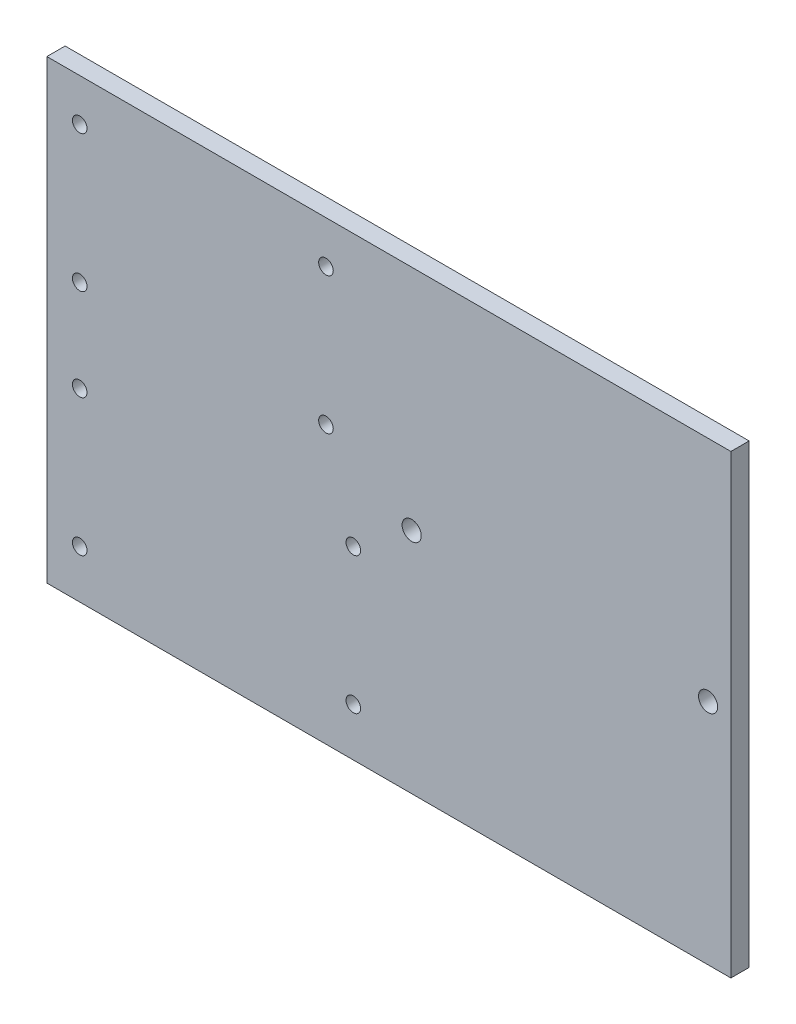
SolidWorks part; units mm, degrees
ref_plane "前视基准面" through (0, 0, 0) normal (0, 0, 1) x (1, 0, 0)
ref_plane "上视基准面" through (0, 0, 0) normal (0, 1, 0) x (1, 0, 0)
ref_plane "右视基准面" through (0, 0, 0) normal (1, 0, 0) x (0, 0, -1)
other "Configuration Table"
sketch "草图1" plane through (0, 0, 0) normal (0, 0, 1) x (1, 0, 0)
  line L0 (97.0297, -3.5891) -> (-52.9703, -3.5891) construction
  line L1 (-52.9703, 46.4109) -> (97.0297, 46.4109)
  line L2 (-52.9703, 46.4109) -> (-52.9703, -53.5891)
  line L3 (-52.9703, -53.5891) -> (97.0297, -53.5891)
  line L4 (97.0297, 46.4109) -> (97.0297, -53.5891)
  line L6 (27.0297, 29.2497) -> (92.0297, 29.2497) construction
  line L7 (27.0297, 29.2497) -> (27.0297, -33.8323) construction
  line L8 (27.0297, -33.8323) -> (92.0297, -33.8323) construction
  line L9 (92.0297, 29.2497) -> (92.0297, -33.8323) construction
  line L10 (-45.7673, -13.0209) -> (14.2327, -13.0209) construction
  line L11 (-45.7673, -13.0209) -> (-45.7673, -43.0209) construction
  line L12 (-45.7673, -43.0209) -> (14.2327, -43.0209) construction
  line L13 (14.2327, -13.0209) -> (14.2327, -43.0209) construction
  line L14 (-45.7673, 37.1291) -> (8.2327, 37.1291) construction
  line L15 (-45.7673, 37.1291) -> (-45.7673, 7.1291) construction
  line L16 (-45.7673, 7.1291) -> (8.2327, 7.1291) construction
  line L17 (8.2327, 37.1291) -> (8.2327, 7.1291) construction
  circle A0 centre (92.0297, -3.5891) radius 2.1
  circle A2 centre (27.0297, -3.5891) radius 2.1
  circle A3 centre (-45.7673, -43.0209) radius 1.6
  circle A4 centre (-45.7673, -13.0209) radius 1.6
  circle A5 centre (14.2327, -13.0209) radius 1.6
  circle A6 centre (14.2327, -43.0209) radius 1.6
  circle A7 centre (-45.7673, 37.1291) radius 1.6
  circle A8 centre (-45.7673, 7.1291) radius 1.6
  circle A9 centre (8.2327, 7.1291) radius 1.6
  circle A10 centre (8.2327, 37.1291) radius 1.6
  dimension "D5" = 4.2
  dimension "D8" = 3.2
  dimension "D11" = 3.2
  dimension "D1" = 150
  dimension "D2" = 100
  dimension "D3" = 65
  dimension "D4" = 5
  dimension "D6" = 60
  dimension "D7" = 30
  dimension "D9" = 30
  dimension "D10" = 54
extrude "凸台-拉伸1" add sketch "草图1" along normal blind 4
